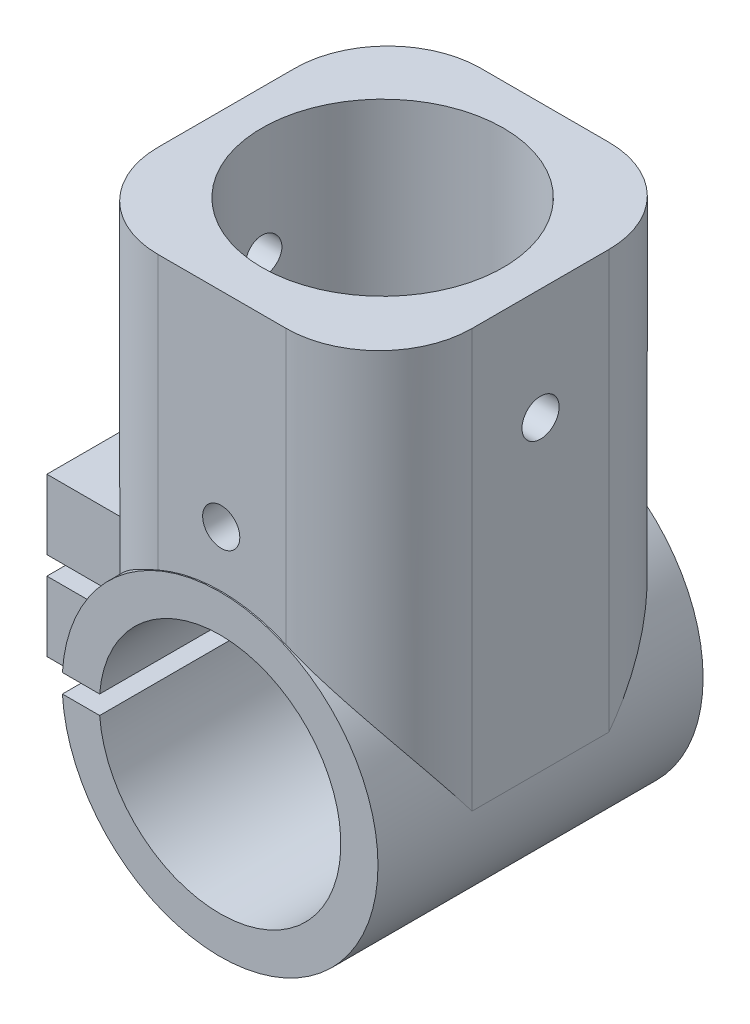
SolidWorks part; units mm, degrees
ref_plane "Спереди" through (0, 0, 0) normal (0, 0, 1) x (1, 0, 0)
ref_plane "Сверху" through (0, 0, 0) normal (0, 1, 0) x (1, 0, 0)
ref_plane "Справа" through (0, 0, 0) normal (1, 0, 0) x (0, 0, -1)
sketch "Эскиз1" plane through (0, 0, 0) normal (0, 0, 1) x (1, 0, 0)
  circle A0 centre (0, 0) radius 12
  circle A1 centre (0, 0) radius 17
extrude "Бобышка-Вытянуть2" add sketch "Эскиз1" along normal blind 35
ref_plane "Плоскость4" through (0, 45, 0) normal (0, 1, 0) x (1, 0, 0)
sketch "Эскиз3" plane through (0, 45, 0) normal (0, 1, 0) x (1, 0, 0)
  line L0 (17, -35) -> (17, 0) construction
  line L13 (-16.7953, -0.1471) -> (17, -0.1471)
  line L14 (-16.7953, -0.1471) -> (-16.7953, -34.8751)
  line L15 (-16.7953, -34.8751) -> (17, -34.8751)
  line L16 (17, -0.1471) -> (17, -34.8751)
  line L17 (-16.7953, -0.1471) -> (-17, 0) construction
  line L18 (-17, 0) -> (-17, -35) construction
  line L19 (-16.7953, -34.8751) -> (-17, -35) construction
  circle A1 centre (0, -17.5) radius 13
extrude "Бобышка-Вытянуть7" add sketch "Эскиз3" against normal blind 45
sketch "Эскиз4" plane through (0, 0, 0) normal (0, 0, -1) x (-1, 0, 0)
  circle A0 centre (0, 0) radius 13
extrude "Вырез-Вытянуть1" cut sketch "Эскиз4" against normal through all
sketch "Эскиз12" plane through (0, 0, 0) normal (0, 0, -1) x (-1, 0, 0)
  line L0 (0, 23) -> (0, 0) construction
  circle A3 centre (0, 23) radius 2
extrude "Вырез-Вытянуть11" cut sketch "Эскиз12" against normal blind 45
sketch "Эскиз15" plane through (-16.7953, 0, 0) normal (-1, 0, 0) x (0, 0, 1)
  line L0 (0, 0) -> (0, 33) construction
  line L1 (0, 33) -> (17.5, 33) construction
  circle A1 centre (17.5, 33) radius 2
extrude "Вырез-Вытянуть12" cut sketch "Эскиз15" against normal blind 45
fillet "Скругление4" radius 10 4 edges at (-16.7953, 23.8152, 0.1471) (17, 22.5, 0.1471) (17, 22.5, 34.8751) (-16.7953, 23.8152, 34.8751)
sketch "Эскиз20" plane through (0, 45, 0) normal (0, 1, 0) x (1, 0, 0)
  circle A3 centre (0, -17.5) radius 13
extrude "Вырез-Вытянуть18" cut sketch "Эскиз20" against normal blind 31
sketch "Эскиз25" plane through (0, 14, 0) normal (0, 1, 0) x (1, 0, 0)
  circle A2 centre (0, -17.5) radius 13
extrude "Бобышка-Вытянуть10" add sketch "Эскиз25" along normal blind 1
sketch "Эскиз26" plane through (-16.7953, 0, 0) normal (-1, 0, 0) x (0, 0, 1)
  line L0 (0, -1) -> (0, 1)
  line L1 (0, 1) -> (35, 1)
  line L2 (0, -1) -> (35, -1)
  line L3 (35, -13) -> (35, 13) construction
  line L4 (35, 1) -> (35, -1)
  point P0 (0, 0)
  point P4 (0, 0)
extrude "Вырез-Вытянуть19" cut sketch "Эскиз26" against normal up to next and the other way through all
sketch "Эскиз27" plane through (-16.7953, 0, 0) normal (-1, 0, 0) x (0, 0, 1)
  line L0 (0, 1) -> (35, 1) construction
  line L1 (10.1471, 8.5) -> (24.8471, 8.5)
  line L2 (10.1471, 8.5) -> (10.1471, 1)
  line L3 (10.1471, 1) -> (24.8471, 1)
  line L4 (24.8471, 8.5) -> (24.8471, 1)
  line L5 (10.1471, -1) -> (24.8471, -1)
  line L6 (10.1471, -1) -> (10.1471, -8.5)
  line L7 (10.1471, -8.5) -> (24.8471, -8.5)
  line L8 (24.8471, -1) -> (24.8471, -8.5)
  line L9 (35, -1) -> (0, -1) construction
  line L10 (10.1471, 45) -> (10.1471, 2.6303) construction
extrude "Бобышка-Вытянуть11" add sketch "Эскиз27" along normal blind 12 and the other way blind 3
sketch "Эскиз28" plane through (0, 8.5, 0) normal (0, 1, 0) x (1, 0, 0)
  line L0 (-16.7953, -10.1471) -> (-28.7953, -10.1471) construction
  line L2 (-22.7953, -10.1471) -> (-22.7953, -17.4971) construction
  line L3 (-22.7953, -17.4971) -> (-28.7953, -17.4971) construction
  line L5 (-28.7953, -24.8471) -> (-28.7953, -10.1471) construction
  line L7 (-25.5953, -17.4971) -> (-24.1953, -19.922)
  line L8 (-24.1953, -19.922) -> (-21.3953, -19.922)
  line L9 (-21.3953, -19.922) -> (-19.9953, -17.4971)
  line L10 (-19.9953, -17.4971) -> (-21.3953, -15.0722)
  line L11 (-21.3953, -15.0722) -> (-24.1953, -15.0722)
  line L12 (-24.1953, -15.0722) -> (-25.5953, -17.4971)
  circle A4 centre (-22.7953, -17.4971) radius 2.8 construction
sketch "Эскиз29" plane through (0, 0, 0) normal (0, 0, -1) x (-1, 0, 0)
  line L0 (3.0481, -12.6475) -> (3.0481, -3.3346)
  line L1 (3.0481, 3.3346) -> (3.0481, 12.6475)
  line L2 (3.0481, 12.6475) -> (3.0481, -12.6475) construction
  arc A0 (3.0481, 12.6475) -> (3.0481, -12.6475) centre (0, 0) ccw
  arc A1 (3.0481, 3.3346) -> (3.0481, -3.3346) centre (0, 0) ccw
extrude "Бобышка-Вытянуть12" add sketch "Эскиз29" against normal blind 5
sketch "Эскиз30" plane through (0, 0, 0) normal (0, 0, -1) x (-1, 0, 0)
  line L1 (-0.5177, 0) -> (-4.5177, 0) construction
  line L2 (-0.5177, 8.75) -> (-0.5177, -8.75) construction
  circle A0 centre (-0.5177, -8.75) radius 1.6
  arc A1 (3.0481, 3.3346) -> (3.0481, -3.3346) centre (0, 0) ccw construction
  circle A2 centre (-0.5177, 8.75) radius 1.6
extrude "Вырез-Вытянуть21" cut sketch "Эскиз30" against normal up to surface (5 mm away) up to face at (2.8554, 0, 5)
extrude "Вырез-Вытянуть22" cut sketch "Эскиз28" against normal blind 3.2
sketch "Эскиз34" plane through (0, 8.5, 0) normal (0, 1, 0) x (1, 0, 0)
  line L0 (-16.7953, -10.1471) -> (-28.7953, -10.1471) construction
  line L2 (-22.7953, -10.1471) -> (-22.7953, -17.4971) construction
  line L3 (-22.7953, -17.4971) -> (-28.7953, -17.4971) construction
  line L5 (-28.7953, -24.8471) -> (-28.7953, -10.1471) construction
  circle A0 centre (-22.7953, -17.4971) radius 2
extrude "Вырез-Вытянуть23" cut sketch "Эскиз34" against normal through all
